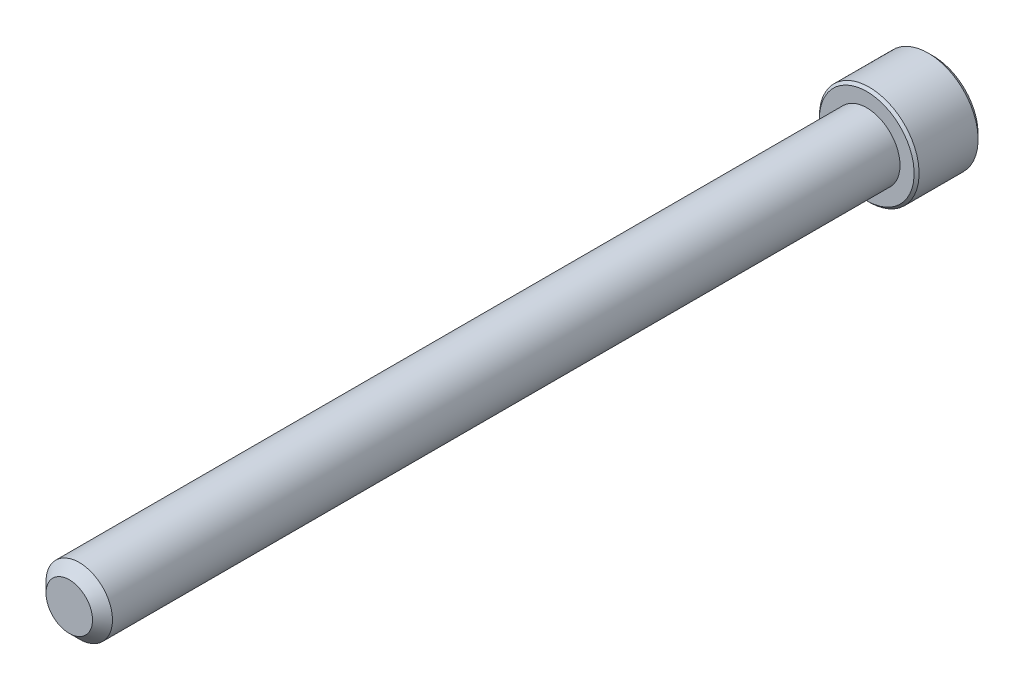
SolidWorks part; units mm, degrees
ref_plane "Front Plane" through (0, 0, 0) normal (0, 0, 1) x (1, 0, 0)
ref_plane "Top Plane" through (0, 0, 0) normal (0, 1, 0) x (1, 0, 0)
ref_plane "Right Plane" through (0, 0, 0) normal (1, 0, 0) x (0, 0, -1)
sketch "Sketch0" plane through (0, 0, 0) normal (1, 0, 0) x (0, 0, -1)
  line L0 (0, 0) -> (76.2, 0) construction
  line L1 (0, -3.175) -> (0, 3.175) construction
  line L2 (82.55, -4.7625) -> (82.55, 4.7625) construction
  line L3 (82.55, -2.3813) -> (82.55, 2.3812) construction
  point P2 (82.55, 0)
  point P4 (25.4, 0)
  point P8 (0, 0)
  point P11 (82.55, 0)
  point P14 (82.55, 0)
  dimension "Min Thread" = 25.4
  dimension "OD" = 6.35
  dimension "screw length" = 76.2
  dimension "head depth" = 6.35
  dimension "head dia" = 9.525
  dimension "hex dia" = 4.7625
sketch "Sketch1" plane through (0, 0, 0) normal (0, 0, 1) x (1, 0, 0)
  circle A0 centre (0, 0) radius 3.175
  dimension "OD" = 6.35
extrude "Extrude1" add sketch "Sketch1" against normal blind 76.2
sketch "Sketch2" [suppressed] plane through (0, 0, 0) normal (0, 0, 1) x (1, 0, 0)
  circle A0 centre (0, 0) radius 3.175 construction
  circle A1 centre (0, 0) radius 3.175
chamfer "Chamfer3" distance 0.9525 angle 45 1 edges at (3.175, 0, 0)
sketch "Sketch3" [suppressed] plane through (0, 0, 0) normal (1, 0, 0) x (0, 0, -1)
  line L0 (-1.1113, 3.175) -> (-0.635, 2.3501)
  line L1 (-0.635, 2.3501) -> (-0.4763, 2.3501)
  line L2 (-0.4763, 2.3501) -> (0, 3.175)
  line L3 (-1.1113, 3.175) -> (0, 3.175)
  line L4 (-0.5556, 3.175) -> (-0.5556, 2.3501) construction
  line L5 (-0.8731, 2.7626) -> (-0.2381, 2.7626) construction
  line L6 (0, 3.175) -> (0, -3.175) construction
  dimension "D1" = 0.1588
  dimension "D2" = 0.635
  dimension "D3" = 60
sketch "Sketch6" plane through (0, 0, -76.2) normal (0, 0, -1) x (-1, 0, 0)
  circle A0 centre (0, 0) radius 4.7625
  dimension "head dia" = 9.525
extrude "Extrude2" add sketch "Sketch6" along normal blind 6.35
sketch "Sketch7" plane through (0, 0, -82.55) normal (0, 0, -1) x (-1, 0, 0)
  line L1 (0, 2.7496) -> (-2.3812, 1.3748)
  line L2 (-2.3812, 1.3748) -> (-2.3812, -1.3748)
  line L3 (-2.3812, -1.3748) -> (0, -2.7496)
  line L4 (0, -2.7496) -> (2.3812, -1.3748)
  line L5 (2.3812, -1.3748) -> (2.3812, 1.3748)
  line L6 (2.3812, 1.3748) -> (0, 2.7496)
  circle A0 centre (0, 0) radius 2.3813 construction
  dimension "hex dia" = 4.7625
extrude "Cut-Extrude1" cut sketch "Sketch7" against normal blind 3.5719
sketch "Sketch8" plane through (0, 0, -82.55) normal (0, 0, -1) x (-1, 0, 0)
  circle A0 centre (0, 0) radius 2.7496
extrude "Cut-Extrude2" cut sketch "Sketch8" against normal through all draft 45
chamfer "Chamfer1" distance 0.4763 angle 45 1 edges at (-4.7625, 0, -82.55)
chamfer "Chamfer2" distance 0.2381 angle 45 1 edges at (-4.7625, 0, -76.2)
sketch "Sketch9" plane through (0, 0, 0) normal (1, 0, 0) x (0, 0, -1)
  line L0 (82.55, -4.7625) -> (82.55, 4.7625) construction
  line L2 (76.2, -4.7625) -> (76.2, 4.7625) construction
  line L9 (82.0738, 4.7625) -> (76.4381, 4.7625) construction
  line L10 (0, -3.175) -> (0, 3.175) construction
  line L11 (0, -3.175) -> (0, 3.175)
  line L12 (3.175, -3.175) -> (3.175, 3.175) construction
  point P4 (82.55, 0)
  point P6 (76.2, 0)
  point P14 (3.175, 0)
  point P15 (3.175, -3.175)
  dimension "D1" = 3.175
ref_plane "Contact Plane 1" through (0, 0, -76.2) normal (0, 0, 1) x (1, 0, 0)
ref_axis "Center Axis 1" through (0, 0, 9.7485) along (0, 0, -1)
curve "Helix/Spiral1" [suppressed] pitch 1.27 height 77.47 turns 61 parameters "pitch"=1.27
sweep "Cut-Sweep1" [suppressed] cut profiles "Sketch3" path "Helix/Spiral1"
sketch "Sketch5" [suppressed] plane through (0, 0, 0) normal (1, 0, 0) x (0, 0, -1)
  line L1 (76.2254, 3.175) -> (25.4, 3.175)
  line L2 (76.2254, 3.175) -> (76.2254, 0)
  line L3 (76.2254, 0) -> (24.2444, 0)
  line L4 (0, 0) -> (76.2, 0) construction
  line L5 (25.4, 3.175) -> (24.2444, 0)
  line L6 (0, 0) -> (82.55, 0) construction
  dimension "D1" = 70
  dimension "D3" = 6.3246
revolve "partially thread" [suppressed] add sketch "Sketch5" angle 360 about L6
sketch "Sketch10" [suppressed] plane through (0, 0, -76.2) normal (0, 0, 1) x (1, 0, 0)
  line L0 (-0.5125, 5.0006) -> (0, 4.5244)
  line L1 (0, 4.5244) -> (0.5125, 5.0006)
  line L2 (0, 4.5244) -> (0, 5.0006) construction
  line L3 (-0.5125, 5.0006) -> (0.5125, 5.0006)
  line L4 (0, -5.2316) -> (0, 5.2316) construction
  line L5 (0, 0) -> (0.2492, 4.756) construction
  line L6 (-0.2492, 4.756) -> (0, 0) construction
  circle A2 centre (0, 0) radius 4.7625 construction
  circle A5 centre (0, 0) radius 4.5244 construction
  dimension "D1" = 6
  dimension "D2" = 0.4762
extrude "Cut-Extrude3" [suppressed] cut sketch "Sketch10" against normal through all
pattern_circular "CirPattern1" [suppressed] count 60 over 360 of bodies 108
equation "\"D3@Helix/Spiral1\"=\"pitch@Helix/Spiral1\"+\"screw length@Sketch0\""
equation "\"D1@Sketch3\" = \"pitch@Helix/Spiral1\"*.125"
equation "\"D2@Sketch3\" = \"pitch@Helix/Spiral1\"*.5"
equation "\"D1@Cut-Extrude1\"=\"hex dia@Sketch0\"*.75"
equation "\"D1@Chamfer1\"=\"head dia@Sketch0\"*.05"
equation "\"D1@Chamfer2\" = \"D1@Chamfer1\"/2"
equation "\"D1@Chamfer3\" = \"pitch@Helix/Spiral1\"*.750"
equation "\"D2@Sketch10\"=\"D1@Chamfer1\""
equation "\"D1@CirPattern1\"=\"D3@CirPattern1\"/\"D1@Sketch10\""
equation "\"D1@Sketch9\"=\"pitch@Helix/Spiral1\"*2.5"
equation "\"OD@Sketch1\"=\"OD@Sketch0\""
equation "\"screw length@Extrude1\"=\"screw length@Sketch0\""
equation "\"head depth@Extrude2\"=\"head depth@Sketch0\""
equation "\"head dia@Sketch6\"=\"head dia@Sketch0\""
equation "\"hex dia@Sketch7\"=\"hex dia@Sketch0\""
equation "\"D3@Sketch5\"=\"head depth@Sketch0\"-.001"
